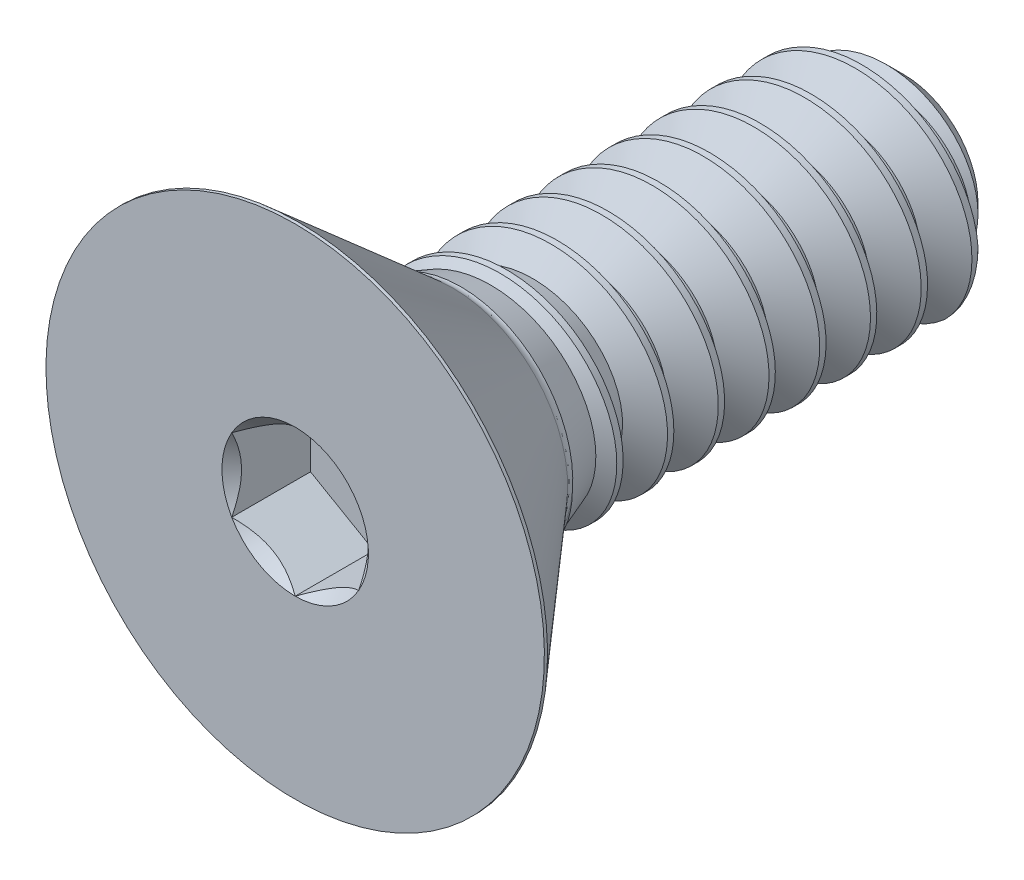
SolidWorks part; units mm, degrees
note: '?' marks a value the reader was unsure of.
ref_plane "Front Plane" through (0, 0, 0) normal (0, 0, 1) x (1, 0, 0)
ref_plane "Top Plane" through (0, 0, 0) normal (0, 1, 0) x (1, 0, 0)
ref_plane "Right Plane" through (0, 0, 0) normal (1, 0, 0) x (0, 0, -1)
sketch "Sketch1" plane through (0, 0, 0) normal (1, 0, 0) x (0, 0, -1)
  line L0 (-4.7625, 0) -> (4.7625, 0) construction
  line L1 (-4.7625, 0) -> (-4.7625, 3.8989)
  line L2 (-4.7625, 3.8989) -> (-4.7132, 3.8989)
  line L3 (-4.7132, 3.8989) -> (-2.2987, 1.8)
  line L4 (-4.7132, -3.8989) -> (-2.2987, -1.8)
  line L5 (4.7625, 0) -> (4.7625, 1.7526)
  line L6 (4.7625, 1.7526) -> (-2.2987, 1.7526)
  line L7 (4.1672, 1.7526) -> (4.7625, 1.1573)
  line L8 (4.7129, 1.8385) -> (5.1098, 1.1511) construction
  line L9 (5.1098, 1.1511) -> (5.5066, 1.8385) construction
  line L10 (5.5066, 1.8385) -> (4.7129, 1.8385) construction
  line L11 (4.7377, 1.7956) -> (5.4818, 1.7956)
  line L12 (5.4818, 1.7956) -> (5.1594, 1.237)
  line L13 (5.1594, 1.237) -> (5.0602, 1.237)
  line L14 (5.0602, 1.237) -> (4.7377, 1.7956)
  line L15 (5.1098, 1.237) -> (5.1098, 1.1511) construction
  line L16 (4.7625, 1.7526) -> (5.457, 1.7526) construction
  line L17 (5.1098, 1.8385) -> (5.1098, 1.7526) construction
  line L18 (4.7625, -1.7526) -> (-2.2987, -1.7526)
  arc A0 (-2.2987, 1.8) -> (-2.172, 1.7526) centre (-2.172, 1.9458) ccw
  point P2 (0, 0)
  point P23 (-3.5306, 0)
  point P27 (5.1098, 1.7956)
  point P30 (3.5719, -1.7526)
  point P34 (-4.7132, -3.8989)
  dimension "Length" = 9.525
  dimension "Head Height" = 2.4638
  dimension "Head Diameter" = 7.7978
  dimension "Countersink Angle" = 82
  dimension "Thread Diameter" = 3.5052
  dimension "D2" = 0.0493
  dimension "Pitch" = 0.7937
  dimension "D4" = 0.0992
  dimension "D3" = 45
  dimension "D5" = 0.5953
  dimension "D6" = 1.2319
  dimension "D1" = 1.1906
sketch "Sketch2" plane through (0, 0, 0) normal (0, 0, 1) x (1, 0, 0)
  line L1 (0, 1.1457) -> (-0.9922, 0.5728)
  line L2 (-0.9922, 0.5728) -> (-0.9922, -0.5728)
  line L3 (-0.9922, -0.5728) -> (0, -1.1457)
  line L4 (0, -1.1457) -> (0.9922, -0.5728)
  line L5 (0.9922, -0.5728) -> (0.9922, 0.5728)
  line L6 (0.9922, 0.5728) -> (0, 1.1457)
  circle A0 centre (0, 0) radius 0.9922 construction
  dimension "Drive Size" = 1.9844
sketch "Sketch11" plane through (0, 0, 0) normal (1, 0, 0) x (0, 0, -1)
  line L0 (-4.7132, 3.8989) -> (-2.2987, 1.8) construction
  line L1 (-4.7625, 0) -> (-4.7625, 3.8989) construction
  line L2 (-4.7132, 3.8989) -> (-2.2987, 1.8)
  line L3 (-4.7625, 0) -> (-4.7625, 3.8989)
  line L4 (-4.7625, 3.8989) -> (-4.7132, 3.8989) construction
  line L5 (-4.7625, 3.8989) -> (-4.7132, 3.8989)
  line L6 (-2.172, 1.7526) -> (4.1672, 1.7526)
  line L7 (4.1672, 1.7526) -> (4.7625, 1.1573)
  line L8 (4.7625, 1.1573) -> (4.7625, 0)
  line L9 (4.7625, 0) -> (-4.7625, 0)
  arc A0 (-2.2987, 1.8) -> (-2.172, 1.7526) centre (-2.172, 1.9458) ccw construction
  arc A1 (-2.2987, 1.8) -> (-2.172, 1.7526) centre (-2.172, 1.9458) ccw
revolve "Revolve1" add sketch "Sketch11" angle 360 about L9
sketch "Sketch9" plane through (0, 0, 4.7625) normal (0, 0, 1) x (1, 0, 0)
  line L0 (0.9922, -0.5728) -> (0.9922, 0.5728) construction
  line L1 (0, -1.1457) -> (0.9922, -0.5728) construction
  line L2 (-0.9922, -0.5728) -> (0, -1.1457) construction
  line L3 (-0.9922, 0.5728) -> (-0.9922, -0.5728) construction
  line L4 (0, 1.1457) -> (-0.9922, 0.5728) construction
  line L5 (0.9922, 0.5728) -> (0, 1.1457) construction
  line L6 (0.9922, -0.5728) -> (0.9922, 0.5728)
  line L7 (0, -1.1457) -> (0.9922, -0.5728)
  line L8 (-0.9922, -0.5728) -> (0, -1.1457)
  line L9 (-0.9922, 0.5728) -> (-0.9922, -0.5728)
  line L10 (0, 1.1457) -> (-0.9922, 0.5728)
  line L11 (0.9922, 0.5728) -> (0, 1.1457)
sketch "Sketch10" plane through (0, 0, 4.7625) normal (0, 0, 1) x (1, 0, 0)
  circle A0 centre (0, 0) radius 1.1457
extrude "Cut-Extrude2" cut sketch "Sketch10" against normal up to vertex (1.2319 mm away) draft 45 up to point (0, 0, 3.5306)
extrude "Cut-Extrude1" cut sketch "Sketch9" against normal up to vertex (1.2319 mm away) up to point (0, 0, 3.5306)
ref_plane "Plane1" through (0, 0, 2.172) normal (0, 0, 1) x (1, 0, 0)
split "Split1" trim tools "Plane1" bodies to split 111 resulting bodies 105 106
sketch "Sketch3" plane through (0, 0, -4.7625) normal (0, 0, -1) x (-1, 0, 0)
  circle A0 centre (0, 0) radius 1.7526 construction
  circle A1 centre (0, 0) radius 1.7526
curve "Helix/Spiral1" pitch 0.7937 height 9.525 turns 12
sketch "Sketch4" plane through (0, 0, 0) normal (1, 0, 0) x (0, 0, -1)
  line L0 (4.7377, 1.7956) -> (5.4818, 1.7956) construction
  line L1 (5.0602, 1.237) -> (4.7377, 1.7956) construction
  line L2 (5.1594, 1.237) -> (5.0602, 1.237) construction
  line L3 (5.4818, 1.7956) -> (5.1594, 1.237) construction
  line L4 (4.7377, 1.7956) -> (5.4818, 1.7956)
  line L5 (5.0602, 1.237) -> (4.7377, 1.7956)
  line L6 (5.1594, 1.237) -> (5.0602, 1.237)
  line L7 (5.4818, 1.7956) -> (5.1594, 1.237)
sweep "Cut-Sweep1" cut profiles "Sketch4" path "Helix/Spiral1" align with end faces yes
sketch "Sketch7" plane through (0, 0, 2.172) normal (0, 0, 1) x (1, 0, 0)
  circle A0 centre (0, 0) radius 1.7526
extrude "Boss-Extrude2" add sketch "Sketch7" against normal up to next (6.9345 mm away) draft 20
ref_axis "Axis1" through (0, 0, 5.276) along (0, 0, -1)?
equation "\"D2@Sketch1\"=\"Head Height@Sketch1\"/50"
equation "\"D4@Sketch1\" = \"Pitch@Sketch1\" / 8"
equation "\"D5@Sketch1\"=\"Pitch@Sketch1\"*0.75"
equation "\"D4@Helix/Spiral1\"=\"Pitch@Sketch1\""
equation "\"D3@Helix/Spiral1\"=\"Length@Sketch1\""
equation "\"D6@Sketch1\"=\"Head Height@Sketch1\"/2"
equation "\"D1@Sketch1\"=\"Pitch@Sketch1\"*1.5"
